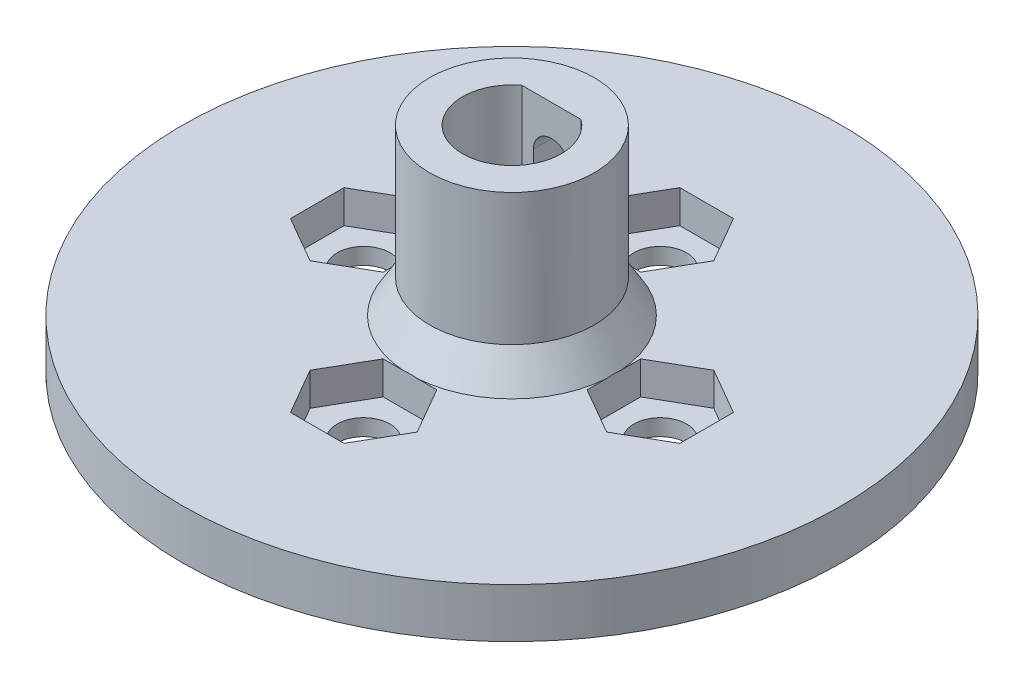
SolidWorks part; units mm, degrees
ref_plane "Front Plane" through (0, 0, 0) normal (0, 0, 1) x (1, 0, 0)
ref_plane "Top Plane" through (0, 0, 0) normal (0, 1, 0) x (1, 0, 0)
ref_plane "Right Plane" through (0, 0, 0) normal (1, 0, 0) x (0, 0, -1)
sketch "Sketch1" plane through (0, 0, 0) normal (0, 1, 0) x (1, 0, 0)
  circle A0 centre (0, 0) radius 20
  dimension "D1" = 40
extrude "Boss-Extrude1" add sketch "Sketch1" along normal blind 3
sketch "Sketch2" plane through (0, 3, 0) normal (0, 1, 0) x (1, 0, 0)
  circle A0 centre (0, 0) radius 5
  dimension "D1" = 10
extrude "Boss-Extrude2" add sketch "Sketch2" along normal blind 10
sketch "Sketch3" plane through (0, 13, 0) normal (0, 1, 0) x (1, 0, 0)
  line L0 (-1.8, 2.4) -> (1.8, 2.4)
  arc A0 (-1.8, 2.4) -> (1.8, 2.4) centre (0, 0) ccw
  dimension "D1" = 6
  dimension "D2" = 2.4
extrude "Cut-Extrude1" cut sketch "Sketch3" against normal blind 11
sketch "Sketch4" plane through (0, 0, 0) normal (0, -1, 0) x (1, 0, 0)
  circle A0 centre (0, 0) radius 1.6
  dimension "D1" = 3.2
extrude "Cut-Extrude2" cut sketch "Sketch4" against normal up to surface (2 mm away) up to face at (0, 2, 0.3)
sketch "Sketch6" plane through (0, 0, 0) normal (0, -1, 0) x (1, 0, 0)
  line L0 (-1000, 0) -> (49000, 0) construction
  line L1 (0, -1000) -> (0, 49000) construction
  line L2 (0, 0) -> (35323.4374, 35323.4374) construction
  circle A0 centre (0, 0) radius 9 construction
  circle A1 centre (0, 9) radius 1.6
  circle A2 centre (0, -9) radius 1.6
  circle A3 centre (9, 0) radius 1.6
  circle A4 centre (-9, 0) radius 1.6
  dimension "D1" = 18
  dimension "D2" = 3.2
extrude "Cut-Extrude3" cut sketch "Sketch6" against normal up to surface (3 mm away) up to face at (0, 3, 5)
sketch "Sketch7" plane through (0, 3, 0) normal (0, 1, 0) x (1, 0, 0)
  line L0 (-1000, 0) -> (49000, 0) construction
  line L1 (3.25, 9) -> (1.625, 11.8146)
  line L2 (1.625, 11.8146) -> (-1.625, 11.8146)
  line L3 (-1.625, 11.8146) -> (-3.25, 9)
  line L4 (-3.25, 9) -> (-1.625, 6.1854)
  line L5 (-1.625, 6.1854) -> (1.625, 6.1854)
  line L6 (1.625, 6.1854) -> (3.25, 9)
  line L7 (0, -1000) -> (0, 49000) construction
  line L8 (0, 0) -> (35355.3391, 35355.3391) construction
  line L9 (1.625, -6.1854) -> (3.25, -9)
  line L10 (-1.625, -6.1854) -> (1.625, -6.1854)
  line L11 (-3.25, -9) -> (-1.625, -6.1854)
  line L12 (-1.625, -11.8146) -> (-3.25, -9)
  line L13 (1.625, -11.8146) -> (-1.625, -11.8146)
  line L14 (3.25, -9) -> (1.625, -11.8146)
  line L15 (6.1854, 1.625) -> (9, 3.25)
  line L16 (6.1854, -1.625) -> (6.1854, 1.625)
  line L17 (9, -3.25) -> (6.1854, -1.625)
  line L18 (11.8146, -1.625) -> (9, -3.25)
  line L19 (11.8146, 1.625) -> (11.8146, -1.625)
  line L20 (9, 3.25) -> (11.8146, 1.625)
  line L21 (-9, 3.25) -> (-11.8146, 1.625)
  line L22 (-11.8146, 1.625) -> (-11.8146, -1.625)
  line L23 (-11.8146, -1.625) -> (-9, -3.25)
  line L24 (-9, -3.25) -> (-6.1854, -1.625)
  line L25 (-6.1854, -1.625) -> (-6.1854, 1.625)
  line L26 (-6.1854, 1.625) -> (-9, 3.25)
  circle A0 centre (0, 9) radius 2.8146 construction
  circle A1 centre (0, -9) radius 2.8146 construction
  circle A2 centre (9, 0) radius 2.8146 construction
  circle A3 centre (-9, 0) radius 2.8146 construction
  circle A4 centre (0, -9) radius 1.6 construction
  dimension "D1" = 6.5
extrude "Cut-Extrude4" cut sketch "Sketch7" against normal blind 2
sketch "Sketch8" plane through (0, 0, -2.4) normal (0, 0, 1) x (1, 0, 0)
  line L0 (0, 6) -> (0, 10) construction
  line L1 (-1.1, 6) -> (-1.1, 10)
  line L2 (1.1, 6) -> (1.1, 10)
  line L3 (1.8, 2) -> (-1.8, 2) construction
  line L4 (1.8, 13) -> (-1.8, 13) construction
  arc A0 (-1.1, 6) -> (1.1, 6) centre (0, 6) ccw
  arc A1 (1.1, 10) -> (-1.1, 10) centre (0, 10) ccw
  point P3 (0, 8)
  dimension "D2" = 4
  dimension "D1" = 2.2
  dimension "D3" = 3
extrude "Cut-Extrude5" cut sketch "Sketch8" against normal up to surface (2.4775 mm away) up to face at (0, 13, 5)
fillet "Fillet1" [suppressed] radius 1.4
ref_point "Point2"
ref_plane "Plane1" through (0, 0, 0) normal (0.7071, 0, 0.7071) x (0.7071, 0, -0.7071)
chamfer "Chamfer2" distance 1.2 distance2 2 1 edges at (0, 3, 5) first distance on face at (0, 3, -9)
